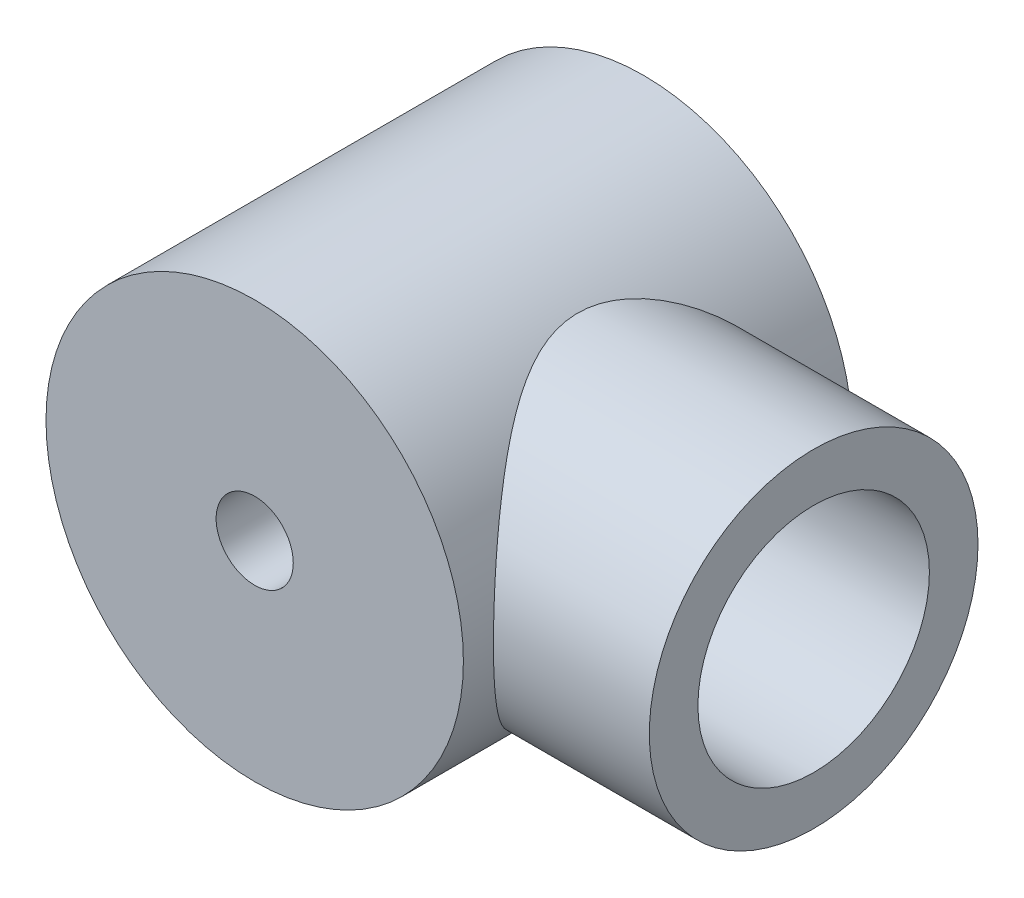
SolidWorks part; units mm, degrees
ref_plane "Front Plane" through (0, 0, 0) normal (0, 0, 1) x (1, 0, 0)
ref_plane "Top Plane" through (0, 0, 0) normal (0, 1, 0) x (1, 0, 0)
ref_plane "Right Plane" through (0, 0, 0) normal (1, 0, 0) x (0, 0, -1)
sketch "Sketch1" plane through (0, 0, 0) normal (0, 0, 1) x (1, 0, 0)
  circle A0 centre (0, 0) radius 1.5875
  circle A1 centre (0, 0) radius 8.5875
  dimension "D1" = 3.175
  dimension "D2" = 7
extrude "Boss-Extrude2" add sketch "Sketch1" along normal blind 8 and the other way blind 8 contours A1 | A0
sketch "Sketch2" plane through (0, 0, 0) normal (1, 0, 0) x (0, 0, -1)
  circle A0 centre (0, 0) radius 6.7625
  circle A1 centre (0, 0) radius 4.7625
  dimension "D1" = 9.525
  dimension "D2" = 2
extrude "Boss-Extrude3" add sketch "Sketch2" along normal blind 15 contours A1 | A0
sketch "Sketch3" plane through (0, 0, 0) normal (0, 0, 1) x (1, 0, 0)
  circle A0 centre (0, 0) radius 1.5875
  dimension "D1" = 3.175
extrude "Cut-Extrude1" cut sketch "Sketch3" against normal blind 10 and the other way blind 10
